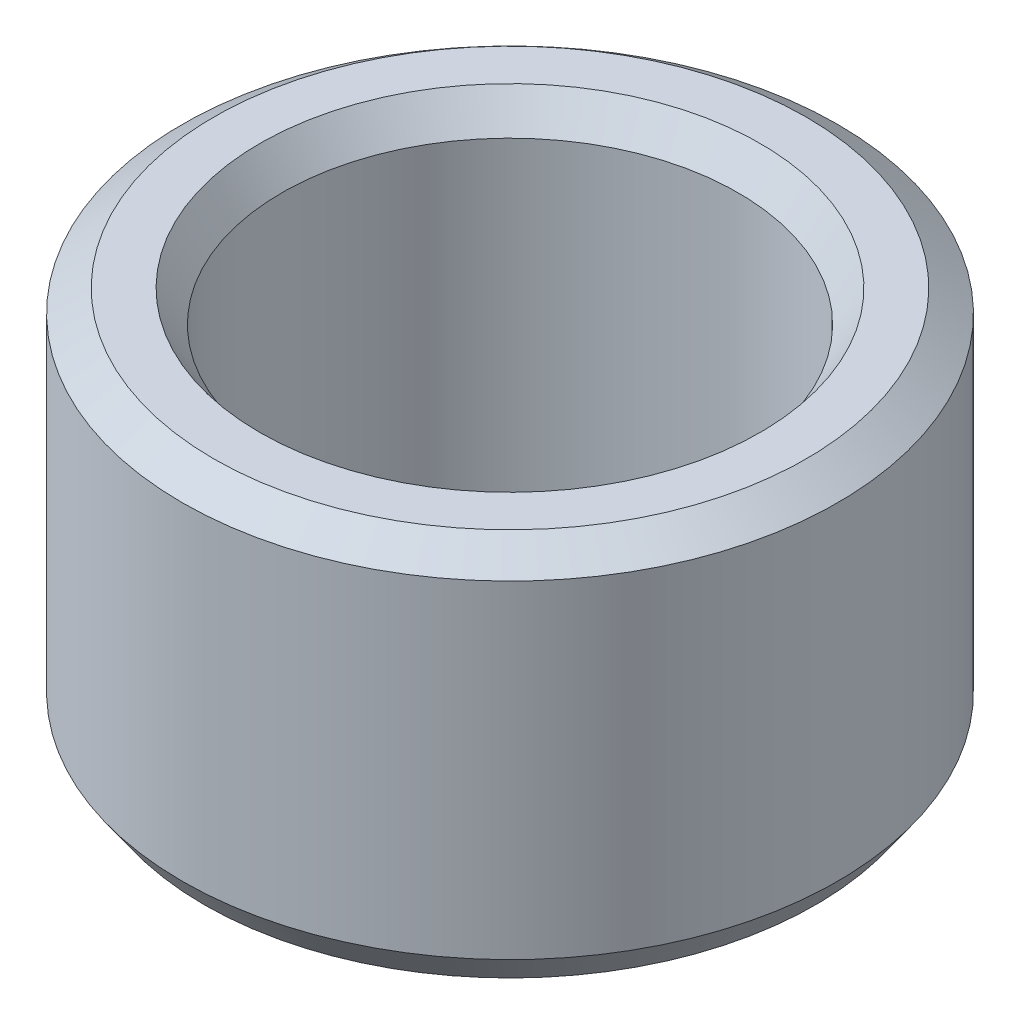
SolidWorks part; units mm, degrees
ref_plane "Front Plane" through (0, 0, 0) normal (0, 0, 1) x (1, 0, 0)
ref_plane "Top Plane" through (0, 0, 0) normal (0, 1, 0) x (1, 0, 0)
ref_plane "Right Plane" through (0, 0, 0) normal (1, 0, 0) x (0, 0, -1)
sketch "Sketch1" plane through (0, 0, 0) normal (0, 1, 0) x (1, 0, 0)
  circle A0 centre (0, 0) radius 55
  dimension "SLEEVE_OD" = 110
extrude "Boss-Extrude1" add sketch "Sketch1" along normal blind 64.0327
sketch "Sketch2" plane through (0, 0, 0) normal (0, 1, 0) x (1, 0, 0)
  circle A0 centre (0, 0) radius 38.2877
  dimension "BORE_D" = 76.5753
extrude "Cut-Extrude1" cut sketch "Sketch2" along normal through all
chamfer "Chamfer1" distance 3.7162 angle 54.949 4 edges at (0, 64.0327, 38.2877) (0, 0, 38.2877) (0, 0, 55) (0, 64.0327, 55) first distance on face at (0, 64.0327, 38.2877) first distance on face at (0, 0, 38.2877) first distance on face at (0, 64.0327, 55)
